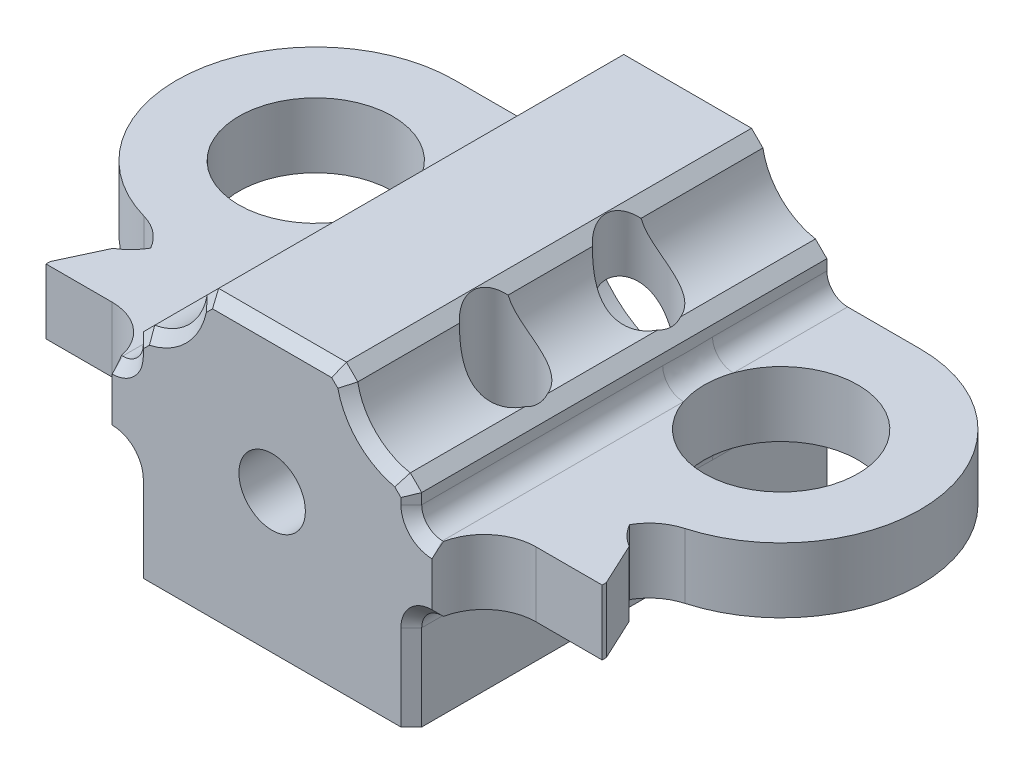
SolidWorks part; units mm, degrees
ref_plane "Front Plane" through (0, 0, 0) normal (0, 0, 1) x (1, 0, 0)
ref_plane "Top Plane" through (0, 0, 0) normal (0, 1, 0) x (1, 0, 0)
ref_plane "Right Plane" through (0, 0, 0) normal (1, 0, 0) x (0, 0, -1)
sketch "Sketch1" plane through (0, 0, 0) normal (0, 0, 1) x (1, 0, 0)
  line L0 (0, 0) -> (0, 69.4209) construction
  line L1 (8.509, 17.018) -> (-8.509, 17.018)
  line L2 (-8.509, 17.018) -> (-8.509, 0)
  line L3 (-8.509, 0) -> (8.509, 0)
  line L4 (8.509, 17.018) -> (8.509, 0)
  point P8 (0, 17.018)
  dimension "D1" = 17.018
  dimension "D2" = 17.018
extrude "Boss-Extrude1" add sketch "Sketch1" along normal blind 25.4
ref_plane "Plane1" through (0, 8.509, 0) normal (0, 1, 0) x (1, 0, 0)
sketch "Sketch2" plane through (0, 0, 0) normal (1, 0, 0) x (0, 0, -1)
  line L0 (-25.4, 8.509) -> (1.0798, 8.509) construction
  line L1 (-25.4, 0) -> (-25.4, 17.018) construction
  line L2 (1.0798, 8.509) -> (1.0798, 14.859)
  line L3 (1.0798, 14.859) -> (-13.97, 14.859)
  line L4 (-13.97, 14.859) -> (-13.97, 10.541)
  line L5 (-13.97, 10.541) -> (-27.617, 10.541)
  line L6 (-15.3578, 14.859) -> (-15.3578, 3.977) construction
  line L7 (-27.617, 10.541) -> (-27.617, 8.509)
  line L8 (9.3599, 8.509) -> (-9.3599, 8.509) construction
  line L10 (-27.617, 8.509) -> (1.0798, 8.509)
  line L11 (-25.4, 17.018) -> (-25.4, 0) construction
  dimension "D1" = 11.43
  dimension "D2" = 2.032
  dimension "D3" = 6.35
revolve "Cut-Revolve1" cut sketch "Sketch2" angle 360 about L10
sketch "Sketch4" plane through (0, 0, 0) normal (0, -1, 0) x (1, 0, 0)
  line L1 (-6, 17.0663) -> (6, 17.0663) construction
  line L2 (-6, 17.0663) -> (-6, 9.0663) construction
  line L3 (-6, 9.0663) -> (6, 9.0663) construction
  line L4 (6, 17.0663) -> (6, 9.0663) construction
  line L5 (-6, 17.0663) -> (6, 9.0663) construction
  line L6 (-6, 9.0663) -> (6, 17.0663) construction
  line L15 (-8.509, 25.4) -> (8.509, 25.4) construction
  circle A0 centre (-6, 17.0663) radius 1.075
  circle A1 centre (5.938, 17.0663) radius 1.075
  circle A2 centre (5.938, 8.9383) radius 1.075
  circle A3 centre (-6, 8.9383) radius 1.075
  point P0 (0, 13.0663)
  dimension "D3" = 2.15
  dimension "D1" = 12
  dimension "D2" = 8
  dimension "D6" = 8.3337
  dimension "D4" = 2
  dimension "D5" = 2
extrude "Cut-Extrude2" cut sketch "Sketch4" against normal through all
sketch "Sketch5" plane through (0, 8.509, 0) normal (0, 1, 0) x (1, 0, 0)
  line L0 (8.509, 0) -> (14.224, 0)
  line L1 (16.9974, -21.9693) -> (15.776, -19.3501)
  line L2 (15.776, -19.3501) -> (14.224, -19.3501)
  line L3 (14.224, -19.3501) -> (14.224, -17.018)
  line L4 (8.509, -25.4) -> (16.9974, -25.4)
  line L5 (14.224, -8.509) -> (21.1828, -23.4322) construction
  line L6 (16.9974, -21.9693) -> (16.9974, -25.4)
  line L7 (8.509, -25.4) -> (8.509, 0) construction
  line L8 (8.509, 0) -> (8.509, -25.4)
  line L10 (0, -25.4) -> (0, 11.748) construction
  line L11 (8.509, -25.4) -> (-8.509, -25.4) construction
  line L12 (14.224, -8.509) -> (14.224, -36.5944) construction
  arc A0 (14.224, 0) -> (14.224, -17.018) centre (14.224, -8.509) cw
  circle A1 centre (14.224, -8.509) radius 4.699
  dimension "D2" = 9.398
  dimension "D4" = 3.81
  dimension "D3" = 5.715
  dimension "D5" = 25
  dimension "D6" = 6.35
extrude "Boss-Extrude2" add sketch "Sketch5" against normal blind 1.9844 and the other way blind 1.9844
mirror "Mirror1" about plane through (0, 0, 0) normal (1, 0, 0) of "Boss-Extrude2"
fillet "Fillet2" radius 3.175 4 edges at (14.224, 8.509, 17.018) (14.224, 8.509, 19.3501) (-14.224, 8.509, 19.3501) (-14.224, 8.509, 17.018)
sketch "Sketch7" plane through (0, 0, 25.4) normal (0, 0, 1) x (1, 0, 0)
  line L0 (0, 19.0675) -> (0, -3.3693) construction
  circle A0 centre (8.509, 17.018) radius 3.9687
  circle A1 centre (-8.509, 17.018) radius 3.9687
  dimension "D1" = 7.9375
extrude "Cut-Extrude3" cut sketch "Sketch7" against normal through all
fillet "Fillet3" radius 1.27 4 edges
chamfer "Chamfer1" distance 0.635 angle 45 4 edges at (8.509, 13.0492, 12.7) (4.5402, 17.018, 12.7) (-4.5402, 17.018, 12.7) (-8.509, 13.0492, 12.7)
chamfer "Chamfer2" distance 0.635 angle 45 21 edges at (-8.881, 6.1527, 25.4) (-16.9974, 8.509, 25.4) (-8.881, 10.8653, 25.4) (-8.1607, 12.7626, 25.4) (-5.7027, 14.2117, 25.4) (-4.2536, 16.6697, 25.4) (8.881, 6.1527, 25.4) (16.9974, 8.509, 25.4) (8.881, 10.8653, 25.4) (8.1607, 12.7626, 25.4) (5.7027, 14.2117, 25.4) (4.2536, 16.6697, 25.4) (0, 17.018, 25.4)
sketch "Sketch8" plane through (0, 17.018, 0) normal (0, 1, 0) x (1, 0, 0)
  line L0 (-16.9974, -22.225) -> (-12.954, -22.225)
  line L1 (-16.9974, -24.765) -> (-16.9974, -21.9693) construction
  line L3 (-9.779, -25.4) -> (-16.3624, -25.4) construction
  line L4 (-16.9974, -22.225) -> (-16.9974, -25.4)
  line L5 (-16.9974, -25.4) -> (-9.779, -25.4)
  line L6 (0, -24.765) -> (0, -9.7356) construction
  line L7 (-3.9052, -24.765) -> (3.9052, -24.765) construction
  line L8 (16.9974, -25.4) -> (9.779, -25.4)
  line L9 (16.9974, -22.225) -> (16.9974, -25.4)
  line L10 (16.9974, -22.225) -> (12.954, -22.225)
  arc A0 (-12.954, -22.225) -> (-9.779, -25.4) centre (-12.954, -25.4) cw
  arc A1 (12.954, -22.225) -> (9.779, -25.4) centre (12.954, -25.4) ccw
  dimension "D1" = 3.175
extrude "Cut-Extrude4" cut sketch "Sketch8" against normal through all
sketch "Sketch10" plane through (0, 17.018, 0) normal (0, 1, 0) x (1, 0, 0)
  line L0 (-0.031, -8.9383) -> (-0.031, -21.1529) construction
  line L1 (-6, -8.9383) -> (5.938, -8.9383) construction
  line L2 (-6, -8.9383) -> (-6, -17.0663) construction
  line L3 (-6, -17.0663) -> (5.938, -17.0663) construction
  line L4 (5.938, -8.9383) -> (5.938, -17.0663) construction
  line L5 (5.938, -13.0023) -> (-11.7995, -13.0023) construction
  circle A0 centre (5.938, -8.9383) radius 2
  circle A1 centre (-6, -8.9383) radius 2
  circle A2 centre (5.938, -17.0663) radius 2
  circle A3 centre (-6, -17.0663) radius 2
  dimension "D1" = 4
extrude "Cut-Extrude6" cut sketch "Sketch10" against normal blind 13.97
